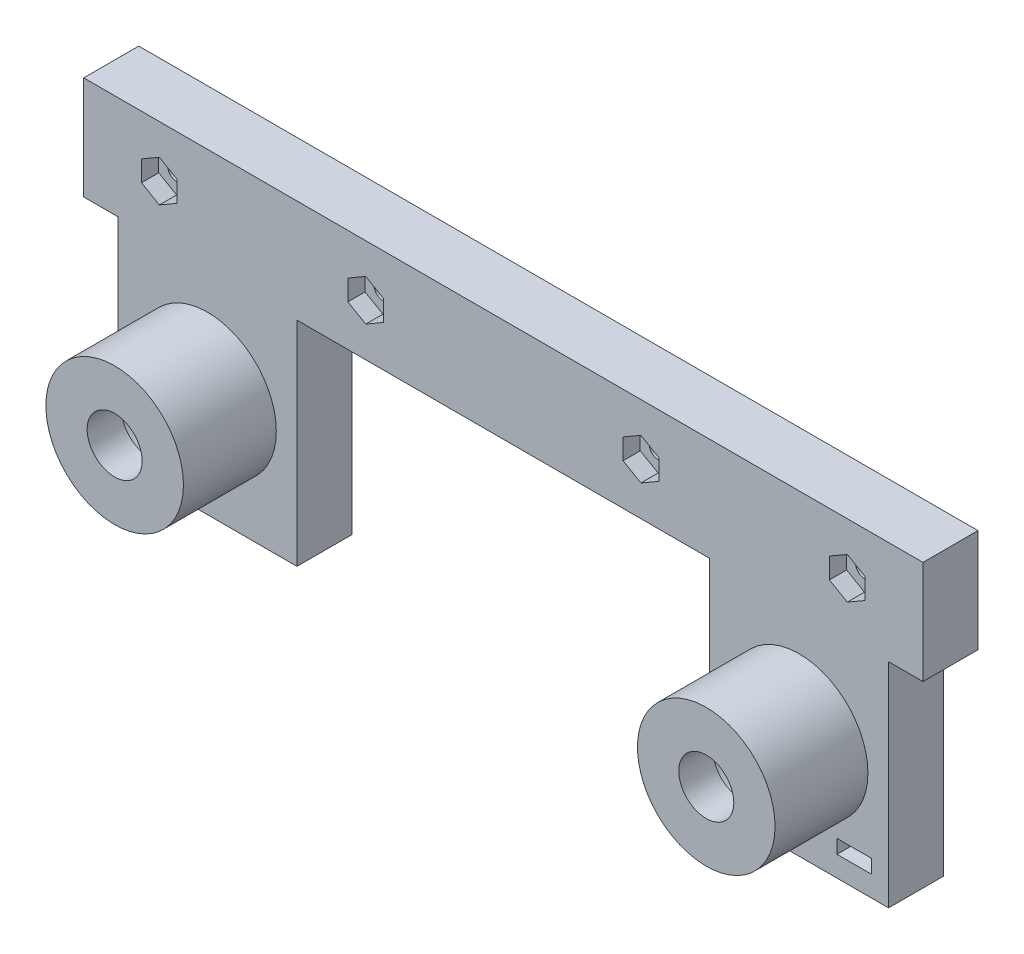
SolidWorks part; units mm, degrees
ref_plane "Front Plane" through (0, 0, 0) normal (0, 0, 1) x (1, 0, 0)
ref_plane "Top Plane" through (0, 0, 0) normal (0, 1, 0) x (1, 0, 0)
ref_plane "Right Plane" through (0, 0, 0) normal (1, 0, 0) x (0, 0, -1)
sketch "Sketch1" plane through (0, 0, 0) normal (0, 0, 1) x (1, 0, 0)
  line L1 (-61, 7.5) -> (61, 7.5)
  line L2 (-61, 7.5) -> (-61, -7.5)
  line L3 (-61, -7.5) -> (61, -7.5)
  line L4 (61, 7.5) -> (61, -7.5)
  line L5 (-61, 7.5) -> (61, -7.5) construction
  line L6 (-61, -7.5) -> (61, 7.5) construction
  point P0 (0, 0)
  dimension "D1" = 15
  dimension "D2" = 122
extrude "Boss-Extrude1" add sketch "Sketch1" along normal blind 8
sketch "Sketch2" plane through (0, 0, 8) normal (0, 0, 1) x (1, 0, 0)
  circle A0 centre (-20, 0) radius 1.3
  circle A1 centre (20, 0) radius 1.3
  circle A2 centre (-50, 0) radius 1.3
  circle A3 centre (50, 0) radius 1.3
  dimension "D3" = 30
  dimension "D4" = 30
  dimension "D5" = 2.6
  dimension "D1" = 20
  dimension "D2" = 20
extrude "Cut-Extrude1" cut sketch "Sketch2" against normal through all both and the other way through all
sketch "Sketch4" plane through (0, 0, 8) normal (0, 0, 1) x (1, 0, 0)
  line L1 (-50, 3) -> (-52.5981, 1.5)
  line L2 (-52.5981, 1.5) -> (-52.5981, -1.5)
  line L3 (-52.5981, -1.5) -> (-50, -3)
  line L4 (-50, -3) -> (-47.4019, -1.5)
  line L5 (-47.4019, -1.5) -> (-47.4019, 1.5)
  line L6 (-47.4019, 1.5) -> (-50, 3)
  line L7 (-20, 3) -> (-22.5981, 1.5)
  line L8 (-22.5981, 1.5) -> (-22.5981, -1.5)
  line L9 (-22.5981, -1.5) -> (-20, -3)
  line L10 (-20, -3) -> (-17.4019, -1.5)
  line L11 (-17.4019, -1.5) -> (-17.4019, 1.5)
  line L12 (-17.4019, 1.5) -> (-20, 3)
  line L13 (20, 3) -> (17.4019, 1.5)
  line L14 (17.4019, 1.5) -> (17.4019, -1.5)
  line L15 (17.4019, -1.5) -> (20, -3)
  line L16 (20, -3) -> (22.5981, -1.5)
  line L17 (22.5981, -1.5) -> (22.5981, 1.5)
  line L18 (22.5981, 1.5) -> (20, 3)
  line L19 (50, 3) -> (47.4019, 1.5)
  line L20 (47.4019, 1.5) -> (47.4019, -1.5)
  line L21 (47.4019, -1.5) -> (50, -3)
  line L22 (50, -3) -> (52.5981, -1.5)
  line L23 (52.5981, -1.5) -> (52.5981, 1.5)
  line L24 (52.5981, 1.5) -> (50, 3)
  circle A0 centre (-50, 0) radius 2.5981 construction
  circle A1 centre (-20, 0) radius 2.5981 construction
  circle A2 centre (20, 0) radius 2.5981 construction
  circle A3 centre (50, 0) radius 2.5981 construction
  dimension "D1" = 6
extrude "Cut-Extrude3" cut sketch "Sketch4" against normal blind 2.5
sketch "Sketch5" plane through (0, 0, 0) normal (0, 0, 1) x (1, 0, 0)
  line L0 (-61, -7.5) -> (61, -7.5) construction
  line L1 (-56, -23) -> (-56, -7.5)
  line L2 (-56, -7.5) -> (-30, -7.5)
  line L3 (-30, -7.5) -> (-30, -23)
  line L4 (30, -23) -> (30, -7.5)
  line L5 (30, -7.5) -> (56, -7.5)
  line L6 (56, -7.5) -> (56, -23)
  line L7 (56, -23) -> (56, -38.5)
  line L8 (56, -38.5) -> (30, -38.5)
  line L9 (30, -38.5) -> (30, -23)
  line L10 (-30, -23) -> (-30, -38.5)
  line L11 (-30, -38.5) -> (-56, -38.5)
  line L12 (-56, -38.5) -> (-56, -23)
  line L13 (-61, -7.5) -> (61, -7.5) construction
  line L14 (-32, -23) -> (-32, -12.9666) construction
  line L15 (32, -23) -> (32, -12.9666) construction
  line L16 (-43, -38.5) -> (-43, -7.5) construction
  circle A0 centre (-43, -23) radius 7.5
  circle A1 centre (43, -23) radius 7.5
  circle A2 centre (-43, -23) radius 11
  circle A3 centre (43, -23) radius 11
  dimension "D1" = 15
  dimension "D4" = 22
  dimension "D2" = 30
  dimension "D3" = 30
  dimension "D5" = 23
  dimension "D6" = 31
  dimension "D7" = 26
  dimension "D8" = 26
  dimension "D9" = 43
extrude "Boss-Extrude2" add sketch "Sketch5" along normal blind 8 contours A2 L2 A0 | A2 L2 L1 | L2 A2 | A2 L3 L2 | A3 L6 L5 | A3 L5 A1 | A3 L5 L4 | L5 A3 region at (-55.5954, -15.25, 0) region at (30.4046, -15.25, 0) region at (-53.6889, -23, 0) region at (32.3111, -23, 0)
sketch "Sketch6" plane through (0, 0, 8) normal (0, 0, 1) x (1, 0, 0)
  circle A0 centre (-43, -23) radius 7.5
  circle A1 centre (-43, -23) radius 10
  circle A2 centre (43, -23) radius 7.5
  circle A3 centre (43, -23) radius 10
  circle A4 centre (-43, -23) radius 7.5 construction
  circle A5 centre (43, -23) radius 7.5 construction
  dimension "D1" = 20
extrude "Boss-Extrude3" add sketch "Sketch6" along normal blind 8.5
sketch "Sketch7" plane through (0, 0, 16.5) normal (0, 0, 1) x (1, 0, 0)
  circle A0 centre (-43, -23) radius 4
  circle A1 centre (-43, -23) radius 10
  circle A2 centre (43, -23) radius 4
  circle A3 centre (43, -23) radius 10
  circle A4 centre (43, -23) radius 10 construction
  circle A5 centre (-43, -23) radius 10 construction
  dimension "D1" = 8
extrude "Boss-Extrude4" add sketch "Sketch7" along normal blind 5
sketch "Sketch8" plane through (0, -38.5, 0) normal (0, -1, 0) x (1, 0, 0)
  line L0 (-56, 4) -> (56, 4) construction
  line L1 (-56, 8) -> (-56, 0) construction
  line L2 (56, 8) -> (56, 0) construction
  line L3 (-56, 8) -> (-56, 0) construction
  circle A0 centre (51, 4) radius 1.3
  circle A1 centre (-51, 4) radius 1.3
  dimension "D3" = 2.6
  dimension "D2" = 5
  dimension "D1" = 5
extrude "Cut-Extrude4" cut sketch "Sketch8" against normal blind 5
sketch "Sketch9" plane through (0, 0, 8) normal (0, 0, 1) x (1, 0, 0)
  line L0 (-56, -38.5) -> (-56, -7.5) construction
  line L5 (-53.5, -33.5) -> (-48.5, -33.5)
  line L6 (-53.5, -33.5) -> (-53.5, -35.5)
  line L7 (48.5, -33.5) -> (53.5, -33.5)
  line L8 (48.5, -33.5) -> (48.5, -35.5)
  line L9 (48.5, -35.5) -> (53.5, -35.5)
  line L10 (53.5, -33.5) -> (53.5, -35.5)
  line L11 (48.5, -33.5) -> (53.5, -35.5) construction
  line L12 (48.5, -35.5) -> (53.5, -33.5) construction
  line L14 (56, -7.5) -> (56, -38.5) construction
  line L16 (-53.5, -35.5) -> (-48.5, -35.5)
  line L17 (-48.5, -33.5) -> (-48.5, -35.5)
  line L18 (-53.5, -33.5) -> (-48.5, -35.5) construction
  line L19 (-53.5, -35.5) -> (-48.5, -33.5) construction
  line L20 (-30, -38.5) -> (-56, -38.5) construction
  point P0 (-51, -34.5)
  point P5 (51, -34.5)
  dimension "D1" = 2
  dimension "D2" = 5
  dimension "D3" = 5
  dimension "D4" = 3
  dimension "D5" = 5
extrude "Cut-Extrude5" cut sketch "Sketch9" against normal through all both and the other way through all
